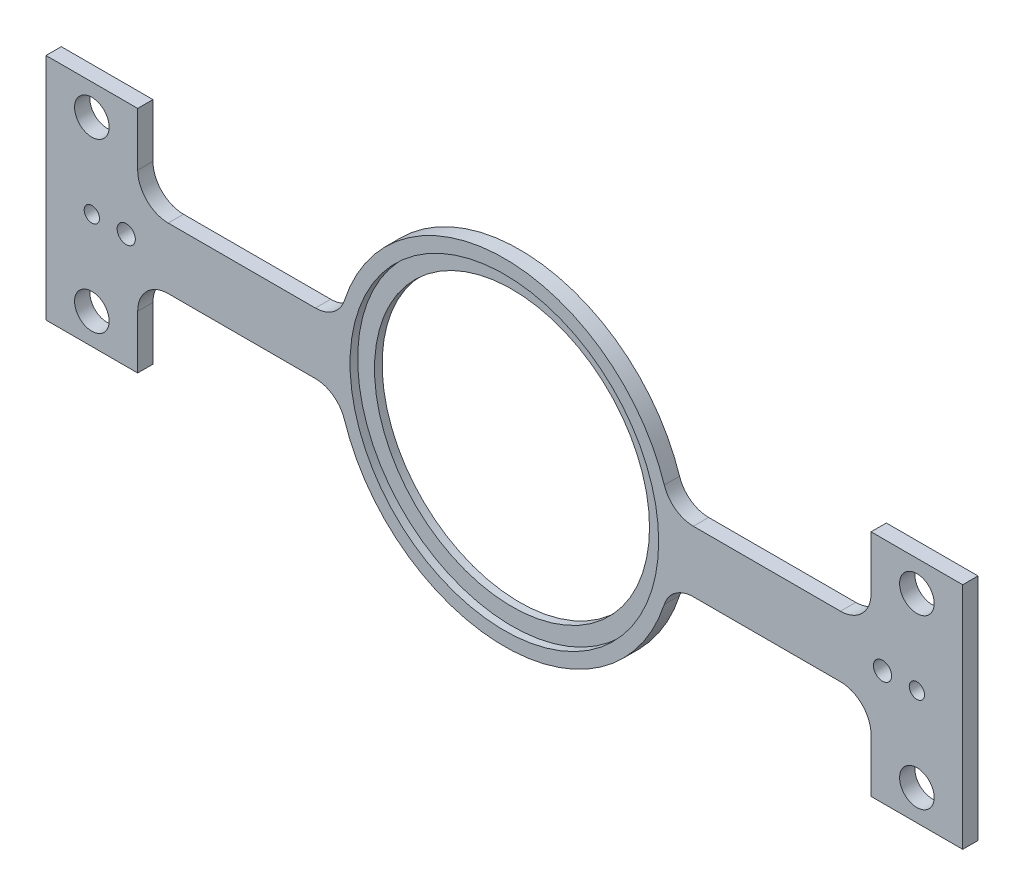
SolidWorks part; units mm, degrees
material "Commercially Pure CP-Ti UNS R50400 (SS)"
ref_plane "Front Plane" through (0, 0, 0) normal (0, 0, 1) x (1, 0, 0)
ref_plane "Top Plane" through (0, 0, 0) normal (0, 1, 0) x (1, 0, 0)
ref_plane "Right Plane" through (0, 0, 0) normal (1, 0, 0) x (0, 0, -1)
sketch "Sketch1" plane through (0, 0, 0) normal (0, 0, 1) x (1, 0, 0)
  line L0 (10.8167, 2) -> (24, 2)
  line L1 (24, 2) -> (24, 7.5)
  line L2 (24, 7.5) -> (30, 7.5)
  line L3 (30, 7.5) -> (30, -7.5)
  line L4 (30, -7.5) -> (24, -7.5)
  line L5 (24, -7.5) -> (24, -2)
  line L6 (24, -2) -> (10.8167, -2)
  line L7 (0, 0) -> (30, 0) construction
  line L8 (0, 0) -> (0, 25.3198) construction
  line L9 (-30, -7.5) -> (-24, -7.5)
  line L10 (-24, -7.5) -> (-24, -2)
  line L11 (-24, -2) -> (-10.8167, -2)
  line L12 (-24, 7.5) -> (-30, 7.5)
  line L13 (-30, 7.5) -> (-30, -7.5)
  line L14 (-24, 2) -> (-24, 7.5)
  line L15 (-10.8167, 2) -> (-24, 2)
  arc A0 (10.8167, 2) -> (-10.8167, 2) centre (0, 0) ccw
  circle A1 centre (0, 0) radius 9
  arc A2 (-10.8167, -2) -> (10.8167, -2) centre (0, 0) ccw
  dimension "D1" = 22
  dimension "D2" = 18
  dimension "D3" = 30
  dimension "D4" = 6
  dimension "D5" = 15
  dimension "D6" = 2
  dimension "D7" = 2
extrude "Boss-Extrude1" add sketch "Sketch1" along normal blind 1
sketch "Sketch2" plane through (0, 0, 1) normal (0, 0, 1) x (1, 0, 0)
  circle A0 centre (0, 0) radius 10.1
  dimension "D1" = 20.2
extrude "Cut-Extrude1" cut sketch "Sketch2" against normal blind 0.5
ref_plane "Plane1" through (0, 0, 0.5) normal (0, 0, 1) x (1, 0, 0)
ref_axis "Axis1" through (-33, 0, 0.5) along (1, 0, 0)
sketch "Sketch3" plane through (30, 0, 0) normal (1, 0, 0) x (0, 0, -1)
  line L0 (-0.5, 7.5) -> (0, 7.5)
  line L1 (-1, 7.5) -> (0, 7.5) construction
  line L2 (0, 7.5) -> (0, 7)
  line L3 (0, -7.5) -> (0, 7.5) construction
  line L4 (0, 7) -> (-0.5, 7.5)
  dimension "D1" = 0.5
extrude "Cut-Extrude2" [suppressed] cut sketch "Sketch3" against normal blind 4
sketch "Sketch6" plane through (0, 0, 0) normal (0, 0, -1) x (-1, 0, 0)
  line L0 (33, 0) -> (-33, 0) construction
  line L1 (-27, -7.5) -> (-27, 0) construction
  line L2 (-24, -7.5) -> (-30, -7.5) construction
  line L3 (27, -7.5) -> (27, 0) construction
  line L4 (30, -7.5) -> (24, -7.5) construction
  circle A0 centre (-27, 0) radius 0.5
  circle A1 centre (27, 0) radius 0.5
  dimension "D1" = 1
extrude "Cut-Extrude3" cut sketch "Sketch6" against normal through all
sketch "Sketch10" plane through (0, 0, 0) normal (0, 0, -1) x (-1, 0, 0)
  point P0 (-27, 0)
  point P1 (27, 0)
hole_wizard "#1 Clearance Hole1" positions "Sketch7" profile "Sketch9" hole size "#1" standard "ANSI Inch" end condition through all
sketch "Sketch7" plane through (0, 0, 0) normal (0, 0, -1) x (-1, 0, 0)
  line L0 (-27, 5.5) -> (-27, -5.5) construction
  line L1 (27, 5.5) -> (27, -5.5) construction
  point P0 (-27, -5.5)
  point P2 (-27, 5.5)
  point P4 (27, 5.5)
  point P6 (27, -5.5)
  dimension "D1" = 11
sketch "Sketch9" plane through (27, -5.5, 0) normal (1, 0, 0) x (0, 1, 0)
  line L0 (0, 0) -> (0, 1)
  line L1 (0, 1) -> (1.1303, 1)
  line L2 (1.1303, 1) -> (1.1303, 0)
  line L5 (1.1303, 0) -> (0, 0)
  line L11 (0, -6.35) -> (0, 107.95) construction
  dimension "Thru Hole Dia." = 2.2606
  dimension "Thru Hole Depth" = 1
hole_wizard "#0-80 Tapped Hole1" positions "Sketch13" profile "Sketch14" tap size "#0-80" standard "ANSI Inch" end condition through all
sketch "Sketch13" plane through (0, 0, 0) normal (0, 0, -1) x (-1, 0, 0)
  line L0 (33, 0) -> (-33, 0) construction
  line L1 (-24, 7.5) -> (-24, 2) construction
  line L2 (24, 2) -> (24, 7.5) construction
  point P0 (-24.75, 0)
  point P4 (24.75, 0)
  dimension "D1" = 0.75
  dimension "D2" = 0.75
sketch "Sketch14" plane through (24.75, 0, 0) normal (1, 0, 0) x (0, 1, 0)
  line L0 (0, 0) -> (0, 1)
  line L1 (0, 1) -> (0.5956, 1)
  line L2 (0.5956, 1) -> (0.5956, 0)
  line L5 (0.5956, 0) -> (0, 0)
  line L11 (0, -6.35) -> (0, 107.95) construction
  dimension "Thru Tap Drill Dia." = 1.1913
  dimension "Thru Tap Drill Depth" = 1
cosmetic thread "Hole Thread1" parameters "D2"=1.524
cosmetic thread "Hole Thread2" parameters "D2"=1.524
fillet "Fillet1" radius 2 8 edges at (-24, -2, 0.5) (-10.8167, -2, 0.5) (10.8167, -2, 0.5) (24, -2, 0.5) (-10.8167, 2, 0.5) (24, 2, 0.5) (10.8167, 2, 0.5) (-24, 2, 0.5)
ref_plane "Plane2" [suppressed] through (0, -0.25, 0.25) normal (0, 0.7071, -0.7071) x (1, 0, 0)
sketch "Sketch4" [suppressed] plane through (0, -0.25, 0.25) normal (0, 0.7071, -0.7071) x (1, 0, 0)
  line L0 (-33, -0.3536) -> (33, -0.3536) construction
  circle A0 centre (0, -0.3536) radius 2
  dimension "D1" = 4
extrude "Boss-Extrude2" [suppressed] add sketch "Sketch4" along normal blind 81 separate body
ref_plane "Plane3" [suppressed] through (0, 0.25, 0.25) normal (0, 0.7071, 0.7071) x (1, 0, 0)
sketch "Sketch5" [suppressed] plane through (0, 0.25, 0.25) normal (0, 0.7071, 0.7071) x (1, 0, 0)
  line L0 (-33, -0.3536) -> (33, -0.3536) construction
  circle A0 centre (0, -0.3536) radius 2
  dimension "D1" = 4
extrude "Boss-Extrude3" [suppressed] add sketch "Sketch5" against normal blind 81
